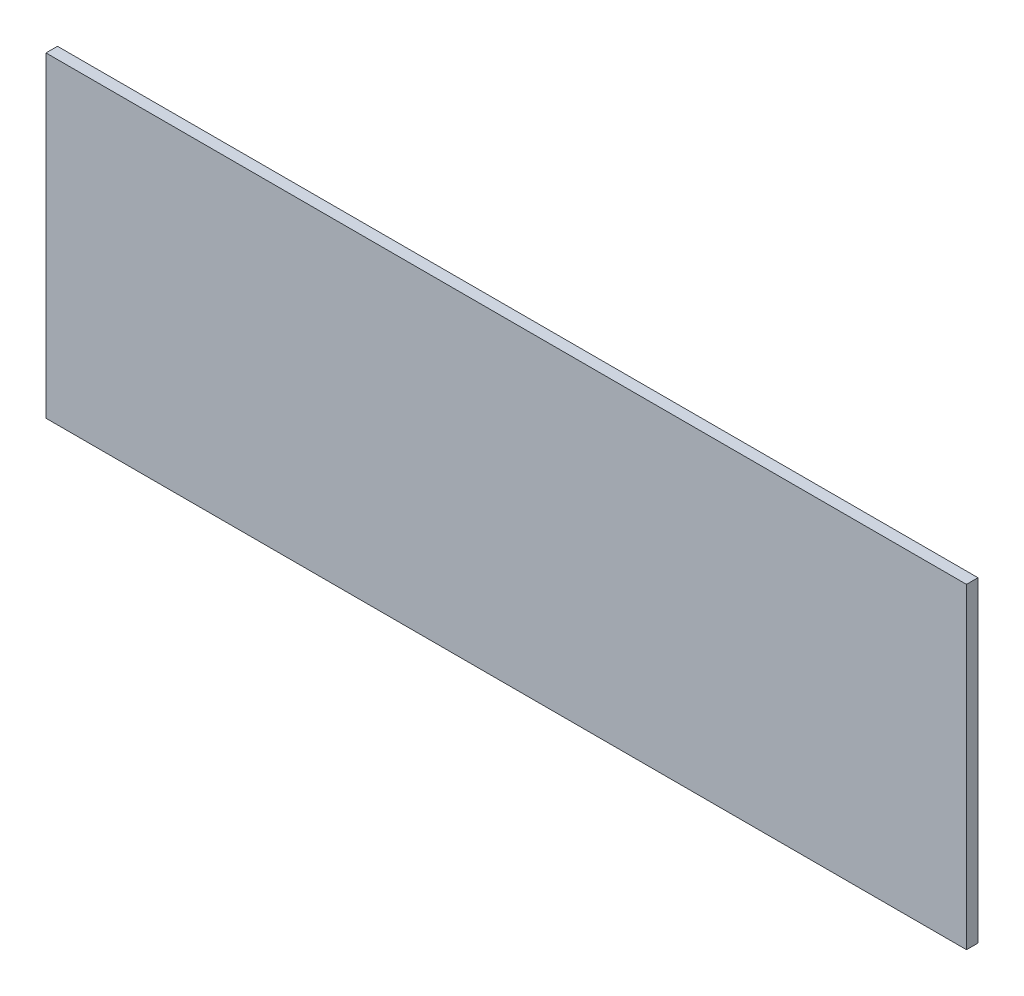
SolidWorks part; units mm, degrees
material "Hexcel AS4C (3000 Filaments)"
ref_plane "Front Plane" through (0, 0, 0) normal (0, 0, 1) x (1, 0, 0)
ref_plane "Top Plane" through (0, 0, 0) normal (0, 1, 0) x (1, 0, 0)
ref_plane "Right Plane" through (0, 0, 0) normal (1, 0, 0) x (0, 0, -1)
sketch "Sketch1" plane through (0, 0, 0) normal (0, 0, 1) x (1, 0, 0)
  line L1 (-40, -13.75) -> (40, -13.75)
  line L2 (-40, -13.75) -> (-40, 13.75)
  line L3 (-40, 13.75) -> (40, 13.75)
  line L4 (40, -13.75) -> (40, 13.75)
  line L5 (-40, -13.75) -> (40, 13.75) construction
  line L6 (-40, 13.75) -> (40, -13.75) construction
  point P0 (0, 0)
  dimension "D1" = 80
  dimension "D2" = 27.5
extrude "Boss-Extrude1" add sketch "Sketch1" along normal blind 1
